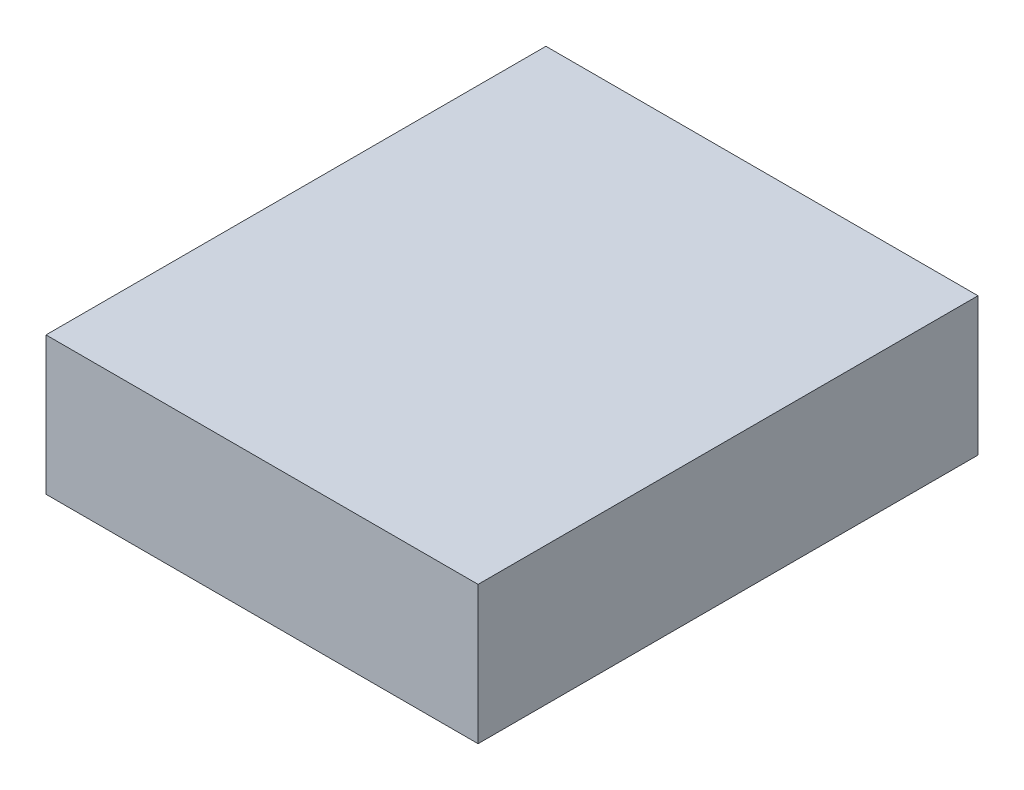
SolidWorks part; units mm, degrees
ref_plane "Front Plane" through (0, 0, 0) normal (0, 0, 1) x (1, 0, 0)
ref_plane "Top Plane" through (0, 0, 0) normal (0, 1, 0) x (1, 0, 0)
ref_plane "Right Plane" through (0, 0, 0) normal (1, 0, 0) x (0, 0, -1)
ref_axis "X-Axis" through (-88.99, 0, 0) along (1, 0, 0)
ref_axis "Y-Axis" through (0, 55, 0) along (0, -1, 0)
ref_axis "Z-Axis" through (0, 0, -88.99) along (0, 0, 1)
sketch "Sketch1" plane through (0, 0, 0) normal (0, 1, 0) x (1, 0, 0)
  line L1 (-15.6524, -18.1102) -> (15.6524, -18.1102)
  line L2 (-15.6524, -18.1102) -> (-15.6524, 18.1102)
  line L3 (-15.6524, 18.1102) -> (15.6524, 18.1102)
  line L4 (15.6524, -18.1102) -> (15.6524, 18.1102)
  line L5 (-15.6524, -18.1102) -> (15.6524, 18.1102) construction
  line L6 (-15.6524, 18.1102) -> (15.6524, -18.1102) construction
  point P0 (0, 0)
extrude "Boss-Extrude1" add sketch "Sketch1" along normal blind 10
